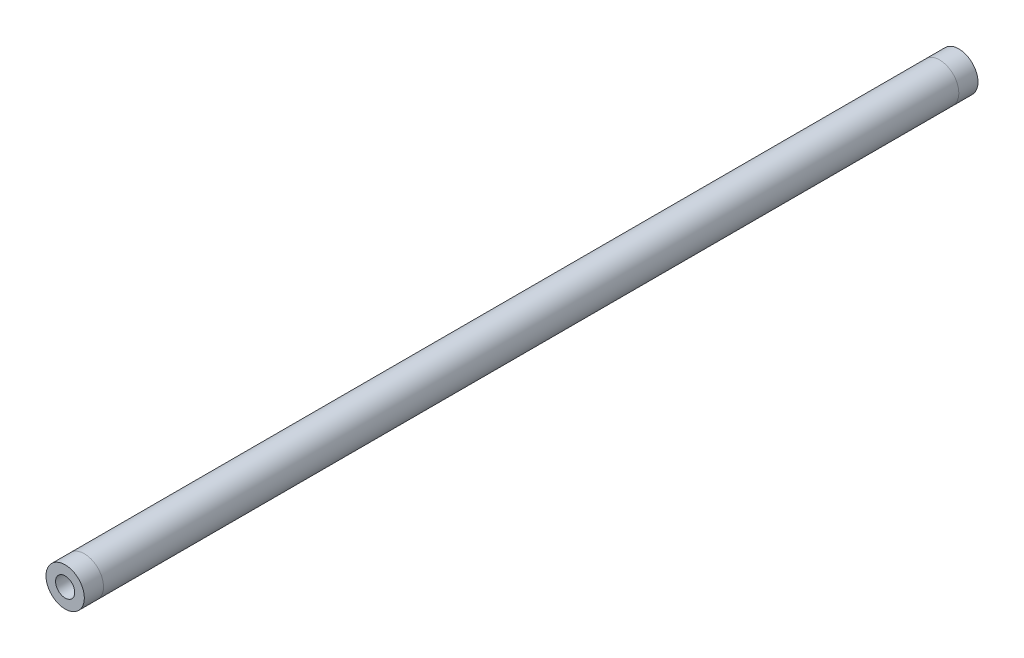
SolidWorks part; units mm, degrees
material "AISI 4130 Steel, normalized at 870C"
ref_plane "Front Plane" through (0, 0, 0) normal (0, 0, 1) x (1, 0, 0)
ref_plane "Top Plane" through (0, 0, 0) normal (0, 1, 0) x (1, 0, 0)
ref_plane "Right Plane" through (0, 0, 0) normal (1, 0, 0) x (0, 0, -1)
sketch "Axis" plane through (0, 0, 0) normal (0, 1, 0) x (1, 0, 0)
  line L0 (0, 0) -> (0, 21.9075) construction
  line L1 (0, 21.9075) -> (0, 317.7011) construction
  line L2 (0, 317.7011) -> (0, 339.6086) construction
  dimension "D1" = 21.9075
  dimension "D2" = 339.6086
sketch "Sketch2" plane through (0, 0, 0) normal (0, 0, 1) x (1, 0, 0)
  circle A0 centre (0, 0) radius 6.35
  circle A1 centre (0, 0) radius 3.175
  circle A2 centre (0, 0) radius 4.7625
  point P6 (0, 0)
  point P7 (0, 0)
  dimension "D1" = 12.7
  dimension "D2" = 6.35
  dimension "D3" = 9.525
extrude "Threaded Insert 1-1" add sketch "Sketch2" against normal blind 6.35 from vertex contours A0 A2 | A2 A1 region at (-6.1704, 0, 0) region at (-4.6278, 0, 0) starting at point (0, 0, -21.9075)
extrude "Threaded Insert 1-2" add sketch "Sketch2<5>" against normal blind 6.35 from surface contours A2 A1 region at (-4.6278, 0, 0) starting at face at (6.35, 0, -28.2575)
sketch "Sketch2<5>" plane through (0, 0, 0) normal (0, 0, 1) x (1, 0, 0) same geometry as "Sketch2"
extrude "Boss-Extrude4" add sketch "Sketch2<7>" along normal blind 6.35 from vertex separate body contours A0 A2 | A2 A1 region at (-6.1704, 0, 0) region at (-4.6278, 0, 0) starting at point (0, 0, -317.7011)
sketch "Sketch2<7>" plane through (0, 0, 0) normal (0, 0, 1) x (1, 0, 0) same geometry as "Sketch2"
extrude "Boss-Extrude5" add sketch "Sketch2<8>" along normal blind 6.35 from surface contours A2 A1 region at (-4.6278, 0, 0) starting at face at (6.35, 0, -311.3511)
sketch "Sketch2<8>" plane through (0, 0, 0) normal (0, 0, 1) x (1, 0, 0) same geometry as "Sketch2"
extrude "Boss-Extrude6" add sketch "Sketch2<9>" against normal up to surface (311.3511 mm away) from surface separate body contours A0 A2 region at (-6.1704, 0, 0) up to face at (6.35, 0, -311.3511) starting at face at (4.7625, 0, -28.2575)
sketch "Sketch2<9>" plane through (0, 0, 0) normal (0, 0, 1) x (1, 0, 0) same geometry as "Sketch2"
equation "\"Tube Outer Diameter\"= .5"
equation "\"Tube Inner Diameter\"= .375"
equation "\"Rod end Diameter\"= .25"
equation "\"Threaded Insert Out\"= .25"
equation "\"Threaded Insert In\"= .25'`"
equation "\"D1@Sketch2\"=\"Tube Outer Diameter\""
equation "\"D2@Sketch2\"=\"Rod end Diameter\""
equation "\"D1@Threaded Insert 1-1\" = \"Threaded Insert Out\""
equation "\"D3@Sketch2\"=\"Tube Inner Diameter\""
equation "\"D1@Threaded Insert 1-2\" = \"Threaded Insert In\""
equation "\"D1@Boss-Extrude4\"=\"Threaded Insert Out\""
equation "\"D1@Boss-Extrude5\"=\"Threaded Insert In\""
